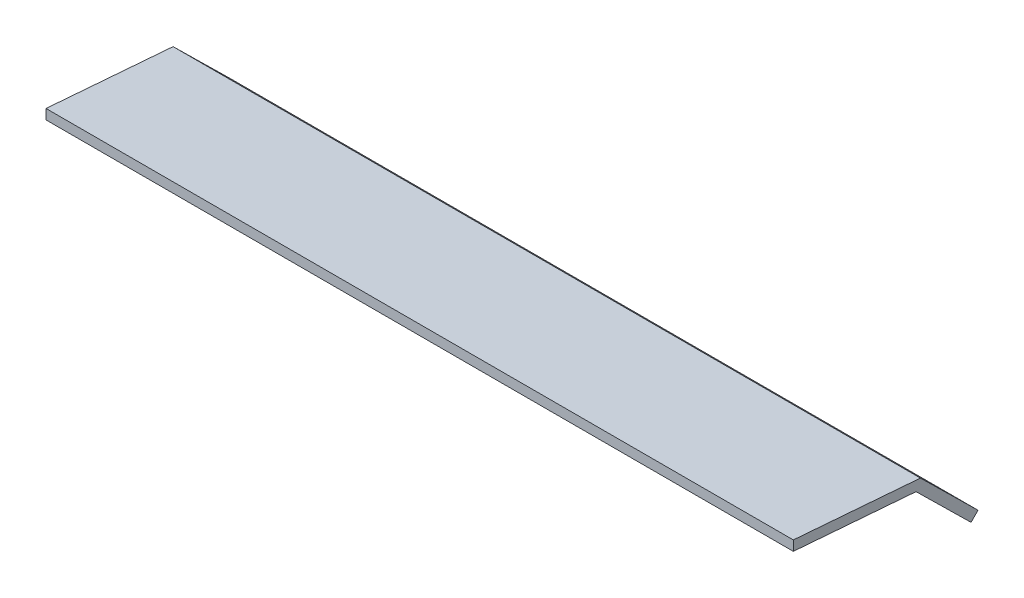
SolidWorks part; units mm, degrees
ref_plane "Front Plane" through (0, 0, 0) normal (0, 0, 1) x (1, 0, 0)
ref_plane "Top Plane" through (0, 0, 0) normal (0, 1, 0) x (1, 0, 0)
ref_plane "Right Plane" through (0, 0, 0) normal (1, 0, 0) x (0, 0, -1)
sketch "Sketch1" plane through (0, 0, 0) normal (1, 0, 0) x (0, 0, -1)
  line L8 (0, 0) -> (0, 3.1848)
  line L9 (0, 3.1848) -> (40.7629, -0.0223)
  line L10 (40.7629, -0.0223) -> (59.239, -18.1789)
  line L11 (59.239, -18.1789) -> (57.0136, -20.4435)
  line L12 (57.0136, -20.4435) -> (39.3618, -3.0969)
  line L13 (39.3618, -3.0969) -> (0, 0)
  point P2 (0, 0)
  point P6 (58.9674, -22.9506)
  point P8 (40.111, -3.1558)
  dimension "D1" = 3.175
  dimension "D2" = 3.175
extrude "Boss-Extrude1" add sketch "Sketch1" along normal mid plane 239.7125
